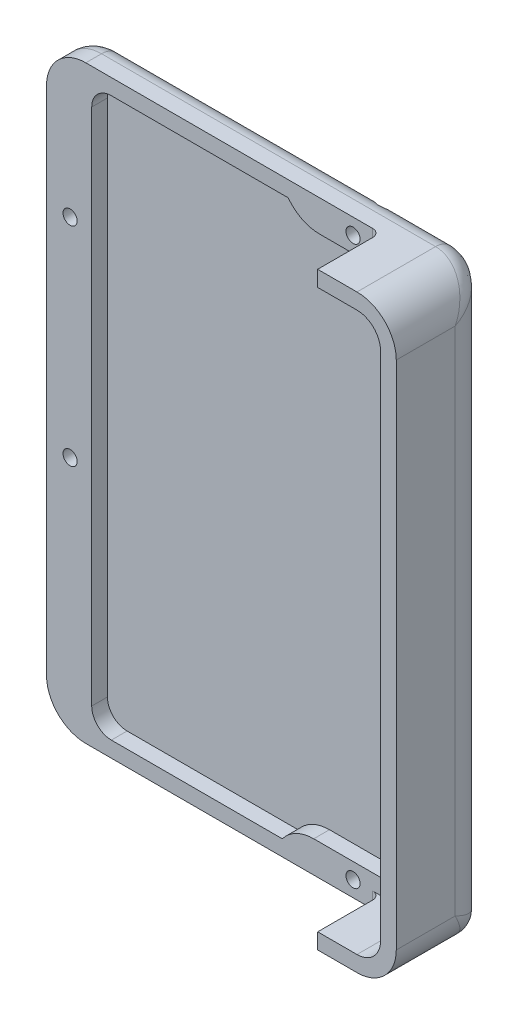
SolidWorks part; units mm, degrees
ref_plane "Front" through (0, 0, 0) normal (0, 0, 1) x (1, 0, 0)
ref_plane "Top" through (0, 0, 0) normal (0, 1, 0) x (1, 0, 0)
ref_plane "Right" through (0, 0, 0) normal (1, 0, 0) x (0, 0, -1)
sketch "Sketch1" plane through (0, 0, 0) normal (0, 0, 1) x (1, 0, 0)
  line L2 (43.8429, 74.3286) -> (-41.1571, 74.3286)
  line L3 (-51.1571, 64.3286) -> (-51.1571, -65.6714)
  line L4 (-41.1571, -75.6714) -> (43.8429, -75.6714)
  line L21 (53.8429, -65.6714) -> (53.8429, 64.3286)
  arc A2 (43.8429, -75.6714) -> (53.8429, -65.6714) centre (43.8429, -65.6714) ccw
  arc A3 (53.8429, 64.3286) -> (43.8429, 74.3286) centre (43.8429, 64.3286) ccw
  arc A4 (-41.1571, 74.3286) -> (-51.1571, 64.3286) centre (-41.1571, 64.3286) ccw
  arc A5 (-51.1571, -65.6714) -> (-41.1571, -75.6714) centre (-41.1571, -65.6714) ccw
  dimension "D5" = 10
  dimension "D6" = 10
  dimension "D7" = 10
  dimension "D8" = 10
  dimension "D1" = 74.3286
  dimension "D2" = 75.6714
  dimension "D3" = 53.8429
  dimension "D4" = 51.1571
  dimension "D9" = 85
  dimension "D10" = 85
  dimension "D11" = 130
  dimension "D12" = 130
  dimension "D13" = 10
  dimension "D14" = 10
  dimension "D15" = 10
  dimension "D16" = 10
extrude "Boss-Extrude1" add sketch "Sketch1" along normal blind 9
sketch "Sketch2" plane through (0, 0, 9) normal (0, 0, 1) x (1, 0, 0)
  line L1 (33.8429, -71.6714) -> (43.8429, -71.6714)
  line L2 (49.8429, -65.6714) -> (49.8429, 64.3286)
  line L3 (43.8429, 70.3286) -> (33.8429, 70.3286)
  line L4 (-51.1571, 64.3286) -> (-51.1571, -65.6714)
  line L5 (-41.1571, -75.6714) -> (43.8429, -75.6714)
  line L6 (53.8429, -65.6714) -> (53.8429, 64.3286)
  line L7 (43.8429, 74.3286) -> (-41.1571, 74.3286)
  line L9 (33.8429, -75.6714) -> (43.8429, -75.6714)
  line L10 (53.8429, -65.6714) -> (53.8429, 64.3286)
  line L11 (43.8429, 74.3286) -> (33.8429, 74.3286)
  line L12 (33.8429, 74.3286) -> (33.8429, 70.3286)
  line L13 (33.8429, -71.6714) -> (33.8429, -75.6714)
  arc A0 (43.8429, -71.6714) -> (49.8429, -65.6714) centre (43.8429, -65.6714) ccw
  arc A1 (49.8429, 64.3286) -> (43.8429, 70.3286) centre (43.8429, 64.3286) ccw
  arc A4 (-41.1571, 74.3286) -> (-51.1571, 64.3286) centre (-41.1571, 64.3286) ccw
  arc A5 (-51.1571, -65.6714) -> (-41.1571, -75.6714) centre (-41.1571, -65.6714) ccw
  arc A6 (43.8429, -75.6714) -> (53.8429, -65.6714) centre (43.8429, -65.6714) ccw
  arc A7 (53.8429, 64.3286) -> (43.8429, 74.3286) centre (43.8429, 64.3286) ccw
  arc A10 (43.8429, -75.6714) -> (53.8429, -65.6714) centre (43.8429, -65.6714) ccw
  arc A11 (53.8429, 64.3286) -> (43.8429, 74.3286) centre (43.8429, 64.3286) ccw
  dimension "D2" = 20
  dimension "D3" = 4
  dimension "D1" = 0
extrude "Boss-Extrude2" add sketch "Sketch2" along normal blind 16
fillet "Fillet2" radius 10 1 edges at (53.8429, -0.6714, 0) tangent propagation no
sketch "Sketch3" plane through (0, 0, 9) normal (0, 0, 1) x (1, 0, 0)
  line L0 (33.8429, 74.3286) -> (-41.1571, 74.3286) construction
  line L1 (53.8429, -65.6714) -> (53.8429, 64.3286) construction
  line L2 (-41.1571, -75.6714) -> (33.8429, -75.6714) construction
  line L3 (-51.1571, 64.3286) -> (-51.1571, -65.6714) construction
  circle A0 centre (26.8429, 70.3286) radius 1.8
  circle A1 centre (26.8429, -71.6714) radius 1.8
  circle A2 centre (-45.1571, 38.3286) radius 1.8
  circle A3 centre (-45.1571, -14.6714) radius 1.8
  point P0 (26.8429, -71.6714)
  point P1 (-45.1571, -14.6714)
  point P3 (-45.1571, 38.3286)
  point P5 (26.8429, 70.3286)
  dimension "D7" = 3.6
  dimension "D8" = 3.6
  dimension "D9" = 3.6
  dimension "D10" = 3.6
  dimension "D1" = 4
  dimension "D2" = 27
  dimension "D3" = 4
  dimension "D4" = 6
  dimension "D5" = 36
  dimension "D6" = 53
extrude "Cut-Extrude1" cut sketch "Sketch3" against normal through all
sketch "Sketch4" plane through (0, 0, 0) normal (0, 0, -1) x (-1, 0, 0)
  circle A0 centre (-26.8429, 70.3286) radius 3.3
  circle A1 centre (45.1571, 38.3286) radius 3.3
  circle A2 centre (45.1571, -14.6714) radius 3.3
  circle A3 centre (-26.8429, -71.6714) radius 3.3
  dimension "D1" = 6.6
  dimension "D2" = 6.6
  dimension "D3" = 6.6
  dimension "D4" = 6.6
extrude "Cut-Extrude2" cut sketch "Sketch4" against normal blind 2.5
sketch "Sketch5" plane through (0, 0, 0) normal (0, 0, -1) x (-1, 0, 0)
  line L0 (-7.8429, 64.3286) -> (-7.8429, -65.6714) construction
  line L1 (21.1571, 59.3286) -> (21.1571, -60.6714) construction
  line L5 (-53.8429, -65.6714) -> (-53.8429, 64.3286) construction
  line L6 (41.1571, -75.6714) -> (-43.8429, -75.6714) construction
  line L7 (-43.8429, 74.3286) -> (41.1571, 74.3286) construction
  line L8 (51.1571, 64.3286) -> (51.1571, -65.6714) construction
  text T0 "ANNIN ROBOTICS" font "Impact" height in points 40
  text T1 "AR4" font "Wide Latin" height in points 65
  dimension "D1" = 10
  dimension "D2" = 10
  dimension "D3" = 15
  dimension "D4" = 15
  dimension "D5" = 30
  dimension "D6" = 46
extrude "Cut-Extrude3" cut sketch "Sketch5" against normal blind 2
sketch "Sketch12" plane through (0, 0, 9) normal (0, 0, 1) x (1, 0, 0)
  line L0 (-51.1571, 64.3286) -> (-51.1571, -65.6714) construction
  line L1 (40.8429, -67.6714) -> (16.8429, -67.6714)
  line L7 (18.3429, 66.3286) -> (40.8429, 66.3286)
  line L8 (-34.6571, 70.3286) -> (10.3429, 70.3286)
  line L11 (-39.6571, -66.6714) -> (-39.6571, 65.3286)
  line L14 (8.8429, -71.6714) -> (-34.6571, -71.6714)
  line L15 (33.8429, 74.3286) -> (-41.1571, 74.3286) construction
  line L16 (-41.1571, -75.6714) -> (33.8429, -75.6714) construction
  line L18 (49.8429, 64.3286) -> (49.8429, -65.6714) construction
  line L19 (33.8429, -71.6714) -> (33.8429, -75.6714) construction
  line L20 (45.8429, 61.3286) -> (45.8429, -62.6714)
  arc A2 (10.3429, 70.3286) -> (18.3429, 66.3286) centre (18.3429, 76.3286) ccw
  arc A11 (16.8429, -67.6714) -> (8.8429, -71.6714) centre (16.8429, -77.6714) ccw
  arc A12 (-34.6571, 70.3286) -> (-39.6571, 65.3286) centre (-34.6571, 65.3286) ccw
  arc A13 (-34.6571, -71.6714) -> (-39.6571, -66.6714) centre (-34.6571, -66.6714) cw
  arc A14 (40.8429, -67.6714) -> (45.8429, -62.6714) centre (40.8429, -62.6714) ccw
  arc A15 (45.8429, 61.3286) -> (40.8429, 66.3286) centre (40.8429, 61.3286) ccw
  dimension "D1" = 17
  dimension "D3" = 5
  dimension "D8" = 10
  dimension "D9" = 10
  dimension "D13" = 5
  dimension "D2" = 11.5
  dimension "D4" = 50
  dimension "D5" = 8
  dimension "D6" = 48.5
  dimension "D7" = 8
  dimension "D10" = 4
  dimension "D11" = 4
  dimension "D12" = 4
extrude "Cut-Extrude5" cut sketch "Sketch12" against normal blind 4
fillet "Fillet4" radius 2 2 edges at (33.8429, 72.3286, 9) (33.8429, -73.6714, 9)
fillet "Fillet5" radius 5 7 edges at (50.9139, 71.3996, 2.9289) (1.3429, 74.3286, 0) (-48.2282, 71.3996, 0) (-51.1571, -0.6714, 0) (-48.2282, -72.7425, 0) (50.9139, -72.7425, 2.9289) (1.3429, -75.6714, 0)
